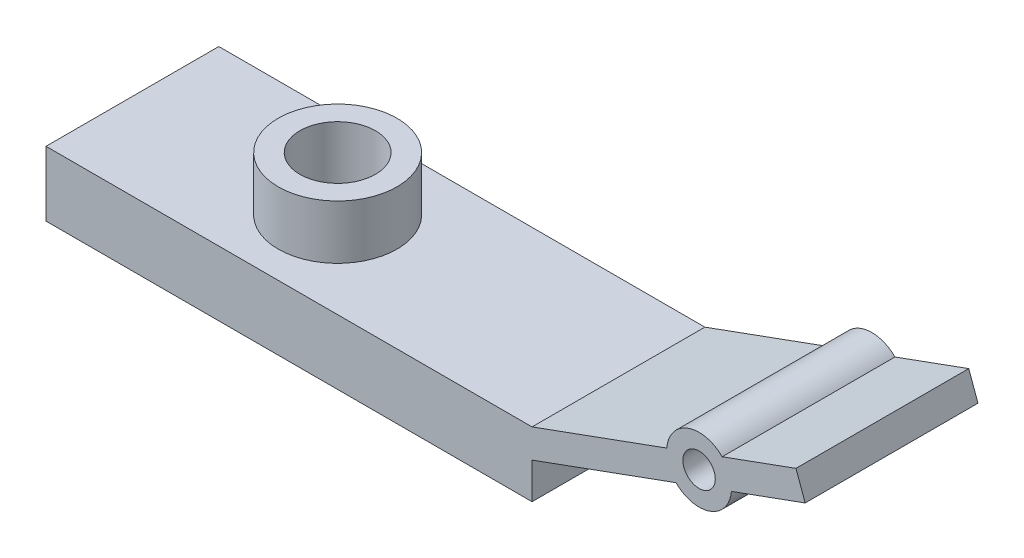
SolidWorks part; units mm, degrees
ref_plane "정면" through (0, 0, 0) normal (0, 0, 1) x (1, 0, 0)
ref_plane "윗면" through (0, 0, 0) normal (0, 1, 0) x (1, 0, 0)
ref_plane "우측면" through (0, 0, 0) normal (1, 0, 0) x (0, 0, -1)
sketch "스케치1" plane through (0, 0, 0) normal (0, 0, 1) x (1, 0, 0)
  line L0 (90, 12) -> (114.9447, 21.0791)
  line L1 (0, 0) -> (90, 0)
  line L2 (0, 0) -> (0, 12)
  line L3 (0, 12) -> (90, 12)
  line L4 (90, 0) -> (90, 6.6791)
  line L5 (138.864, 29.785) -> (140.5741, 25.0866)
  line L6 (140.5741, 25.0866) -> (126.9057, 20.1117)
  line L8 (125.1956, 24.8101) -> (138.864, 29.785)
  line L10 (116.6548, 16.3807) -> (90, 6.6791)
  circle A0 centre (120.9252, 20.5954) radius 3
  arc A1 (116.6548, 16.3807) -> (114.9447, 21.0791) centre (120.9252, 20.5954) ccw
  dimension "D8" = 6
  dimension "D1" = 12
  dimension "D2" = 90
  dimension "D3" = 52
  dimension "D4" = 20
  dimension "D5" = 5
  dimension "D6" = 20
  dimension "D7" = 2.5
extrude "보스-돌출1" add sketch "스케치1" along normal blind 32 contours A1 L0 L3 L2 L1 L4 L10 A0 | A1 L6 L5 L8 region at (55.9667, 7.7796, 0) region at (133.0565, 25.0108, 0)
sketch "스케치2" plane through (0, 12, 0) normal (0, 1, 0) x (1, 0, 0)
  line L0 (0, -32) -> (0, 0) construction
  circle A0 centre (38, -16) radius 7
  circle A1 centre (38, -16) radius 11
  dimension "D1" = 38
  dimension "D2" = 14
  dimension "D3" = 22
extrude "보스-돌출4" add sketch "스케치2" along normal blind 10 contours A1 A0 region at (27.3111, 12, 16)
extrude "컷-돌출1" cut sketch "스케치2<5>" against normal through all contours A0
sketch "스케치2<5>" plane through (0, 12, 0) normal (0, 1, 0) x (1, 0, 0) same geometry as "스케치2"
